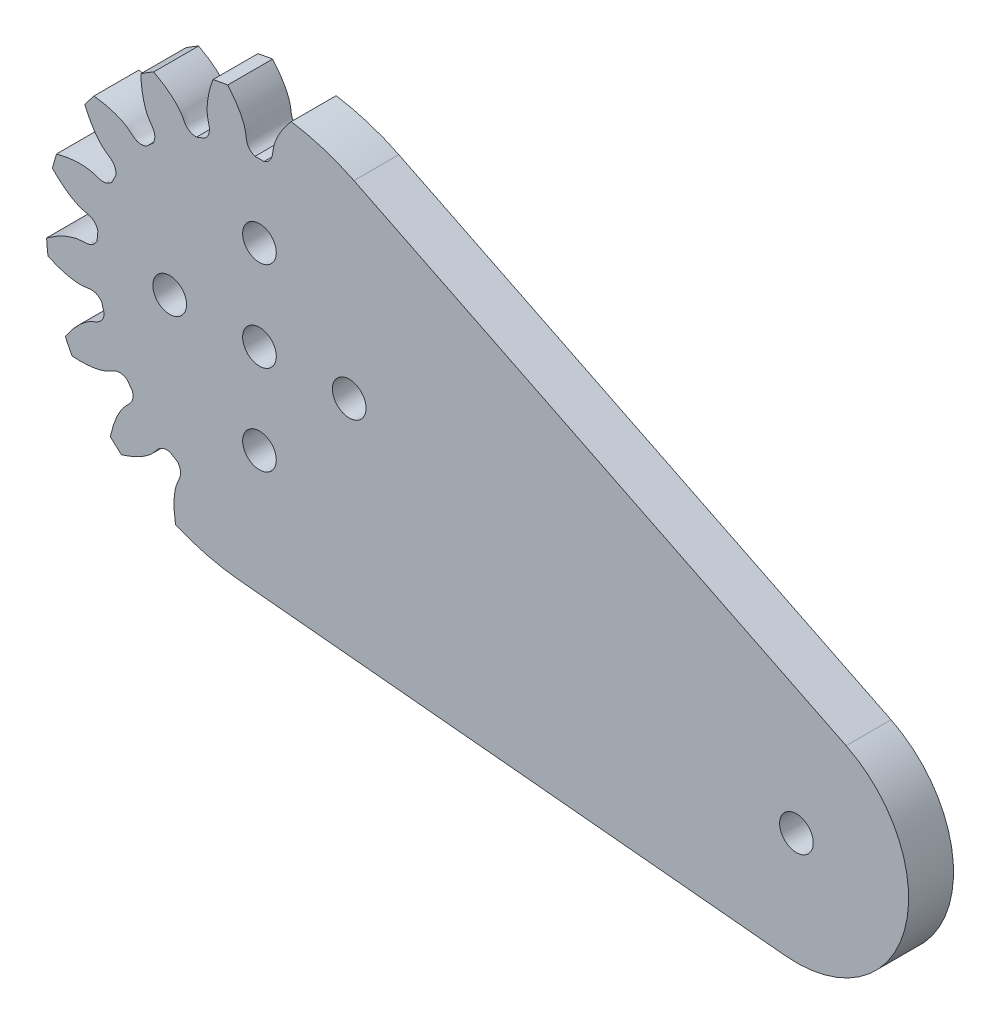
SolidWorks part; units mm, degrees
ref_plane "前视基准面" through (0, 0, 0) normal (0, 0, 1) x (1, 0, 0)
ref_plane "上视基准面" through (0, 0, 0) normal (0, 1, 0) x (1, 0, 0)
ref_plane "右视基准面" through (0, 0, 0) normal (1, 0, 0) x (0, 0, -1)
sketch "草图1" plane through (0, 0, 0) normal (0, 0, 1) x (1, 0, 0)
  circle A0 centre (0, 0) radius 19
extrude "凸台-拉伸1" add sketch "草图1" along normal blind 4
ref_axis "基准轴1" through (0, 0, -0.2) along (0, 0, 1)
sketch "草图2" plane through (0, 0, 0) normal (0, 0, 1) x (1, 0, 0)
  line L0 (0, 0) -> (0, 19) construction
  circle A0 centre (0, 0) radius 19 construction
  arc A1 (0.4034, 14.4944) -> (-0.4034, 14.4944) centre (0, 0) ccw
  arc A2 (6.2313, 21.4814) -> (-6.2313, 21.4814) centre (0, 0) ccw
  spline S0 degree 3 poles (0.4034, 14.4944) (1.2558, 14.8496) (1.1324, 15.5096) (1.2766, 16.1296) (1.29, 16.1823) (1.306, 16.2408) (1.3251, 16.3052) (1.3474, 16.3752) (1.3731, 16.4508) (1.4025, 16.5319) (1.4359, 16.6184) (1.4733, 16.7101) (1.5152, 16.8068) (1.5616, 16.9086) (1.6128, 17.0151) (1.669, 17.1264) (1.7304, 17.2421) (1.7972, 17.3621) (1.8696, 17.4863) (1.9478, 17.6145) (2.032, 17.7465) (2.1224, 17.8821) (2.2191, 18.0211) (2.3223, 18.1634) (2.4322, 18.3086) (2.5489, 18.4566) (2.6727, 18.6072) (2.8035, 18.7601) (2.9417, 18.9152) (3.0873, 19.0722) (3.2404, 19.2308) (3.4012, 19.3908) (3.5698, 19.552) (3.7462, 19.7141) (3.9307, 19.8769) (4.1233, 20.0401) (4.324, 20.2035) (4.533, 20.3667) (4.7503, 20.5295) (4.9761, 20.6917) (5.2103, 20.853) (5.453, 21.0131) (5.7916, 21.2269) (6.0532, 21.3811) (6.2313, 21.4814) knots 0 0 0 0 0.193883 0.199024 0.204851 0.211363 0.21856 0.226443 0.235011 0.244265 0.254205 0.264829 0.27614 0.288136 0.300817 0.314184 0.328236 0.342973 0.358397 0.374505 0.391299 0.408779 0.426944 0.445795 0.465331 0.485552 0.506459 0.528051 0.550329 0.573293 0.596941 0.621276 0.646296 0.672001 0.698392 0.725468 0.753229 0.781677 0.810809 0.840627 0.871131 0.90232 0.934195 1 1 1 1
  spline S1 degree 3 poles (-0.4034, 14.4944) (-1.2558, 14.8496) (-1.1324, 15.5096) (-1.2766, 16.1296) (-1.29, 16.1823) (-1.306, 16.2408) (-1.3251, 16.3052) (-1.3474, 16.3752) (-1.3731, 16.4508) (-1.4025, 16.5319) (-1.4359, 16.6184) (-1.4733, 16.7101) (-1.5152, 16.8068) (-1.5616, 16.9086) (-1.6128, 17.0151) (-1.669, 17.1264) (-1.7304, 17.2421) (-1.7972, 17.3621) (-1.8696, 17.4863) (-1.9478, 17.6145) (-2.032, 17.7465) (-2.1224, 17.8821) (-2.2191, 18.0211) (-2.3223, 18.1634) (-2.4322, 18.3086) (-2.5489, 18.4566) (-2.6727, 18.6072) (-2.8035, 18.7601) (-2.9417, 18.9152) (-3.0873, 19.0722) (-3.2404, 19.2308) (-3.4012, 19.3908) (-3.5698, 19.552) (-3.7462, 19.7141) (-3.9307, 19.8769) (-4.1233, 20.0401) (-4.324, 20.2035) (-4.533, 20.3667) (-4.7503, 20.5295) (-4.9761, 20.6917) (-5.2103, 20.853) (-5.453, 21.0131) (-5.7916, 21.2269) (-6.0532, 21.3811) (-6.2313, 21.4814) knots 0 0 0 0 0.193883 0.199024 0.204851 0.211363 0.21856 0.226443 0.235011 0.244265 0.254205 0.264829 0.27614 0.288136 0.300817 0.314184 0.328236 0.342973 0.358397 0.374505 0.391299 0.408779 0.426944 0.445795 0.465331 0.485552 0.506459 0.528051 0.550329 0.573293 0.596941 0.621276 0.646296 0.672001 0.698392 0.725468 0.753229 0.781677 0.810809 0.840627 0.871131 0.90232 0.934195 1 1 1 1
extrude "切除-拉伸1" cut sketch "草图2" along normal through all
pattern_circular "阵列(圆周)1" count 8 every 21.176 about axis through (0, 0, -0.2) along (0, 0, 1) of "切除-拉伸1"
sketch "草图3" plane through (0, 0, 0) normal (0, 0, 1) x (1, 0, 0)
  circle A0 centre (0, 0) radius 17 construction
  dimension "Dn" = 34
sketch "草图4" plane through (0, 0, 4) normal (0, 0, 1) x (1, 0, 0)
  circle A0 centre (0, 0) radius 1
  dimension "D1" = 2
extrude "切除-拉伸2" cut sketch "草图4" against normal blind 10
sketch "草图5" plane through (0, 0, 4) normal (0, 0, 1) x (1, 0, 0)
  circle A0 centre (0, 8) radius 1.5
  circle A1 centre (8, 0) radius 1.5
  circle A2 centre (0, -8) radius 1.5
  circle A3 centre (-8, 0) radius 1.5
  point P11 (0, 0)
  dimension "D2" = 16
  dimension "D3" = 3
  dimension "D1" = 4
extrude "切除-拉伸3" cut sketch "草图5" against normal blind 10
sketch "草图6" plane through (0, 0, 4) normal (0, 0, 1) x (1, 0, 0)
  circle A0 centre (0, 0) radius 1 construction
  circle A1 centre (0, 0) radius 1
extrude "凸台-拉伸2" add sketch "草图6" against normal up to surface (4 mm away) up to face at (1.5, 8, 0)
sketch "草图7" plane through (0, 0, 0) normal (0, 0, -1) x (-1, 0, 0)
  line L0 (-8.4198, 17.0325) -> (-52.2823, -4.6502)
  line L1 (-46.8993, -23.5694) -> (1.8078, -18.9138)
  line L3 (0, 0) -> (-48091.2822, -13683.1495) construction
  arc A0 (-2.8291, 18.7882) -> (7.4854, -17.4634) centre (0, 0) ccw construction
  arc A1 (-52.2823, -4.6502) -> (-46.8993, -23.5694) centre (-47.8508, -13.6147) ccw
  arc A3 (-8.4198, 17.0325) -> (1.8078, -18.9138) centre (0, 0) ccw
  point P7 (-41.5623, -32.7261)
  point P9 (-45.3597, -26.0679)
  point P11 (-51.0419, -9.2232)
  point P12 (-9.5434, -16.4294)
  point P14 (2.3427, -18.855)
  point P15 (0, 0)
  point P19 (-51.3473, -12.526)
  point P20 (-46.7856, -16.9164)
  point P21 (1.6345, -18.9296)
  dimension "D2" = 10
  dimension "D1" = 49.75
extrude "凸台-拉伸3" add sketch "草图7" against normal up to surface (4 mm away) up to face at (1.5, 8, 4)
sketch "草图8" plane through (0, 0, 0) normal (0, 0, -1) x (-1, 0, 0)
  circle A0 centre (-47.8508, -13.6147) radius 1.5
  arc A1 (-52.2823, -4.6502) -> (-46.8993, -23.5694) centre (-47.8508, -13.6147) ccw construction
  dimension "D1" = 3
extrude "切除-拉伸4" cut sketch "草图8" against normal blind 10
sketch "草图9" plane through (0, 0, 0) normal (0, 0, -1) x (-1, 0, 0)
  circle A0 centre (0, 0) radius 1.5
  dimension "D1" = 3
extrude "切除-拉伸5" cut sketch "草图9" against normal blind 10
